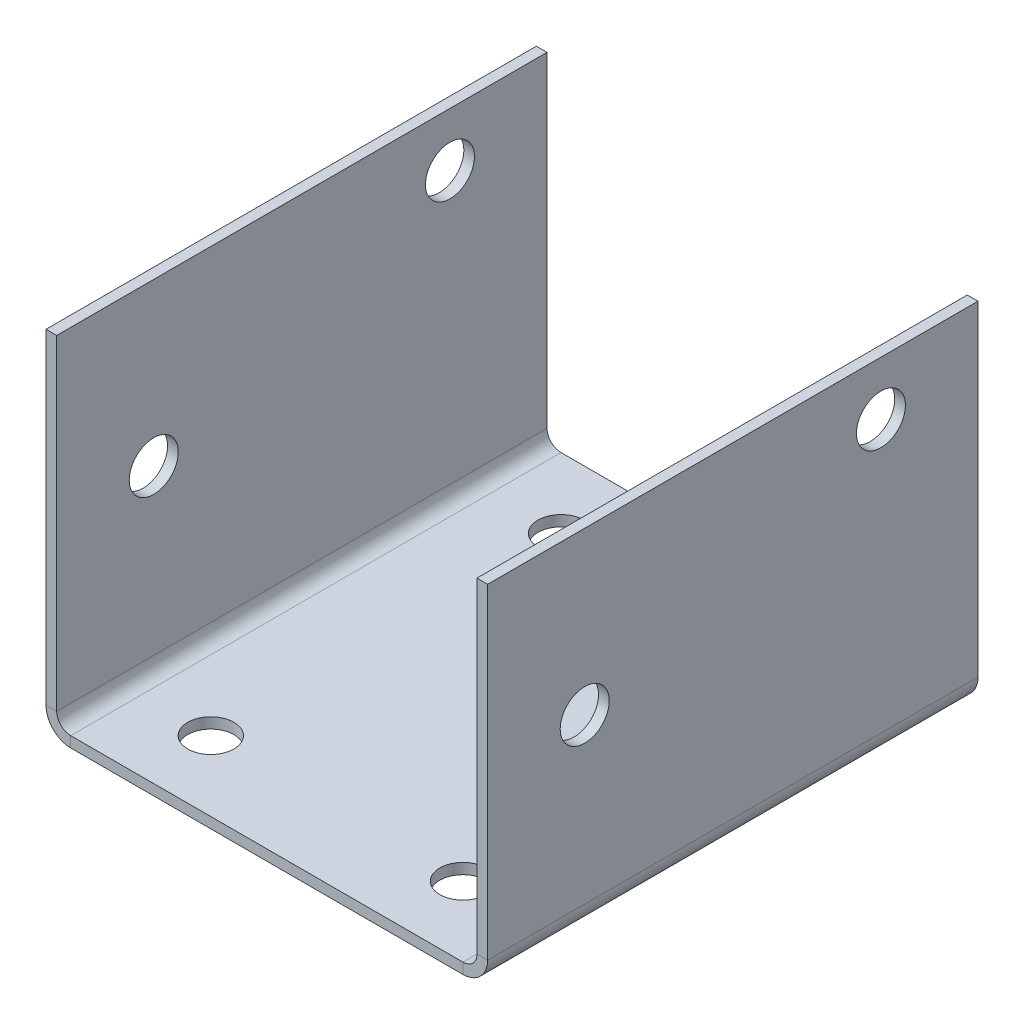
SolidWorks part; units mm, degrees
note: The reader was unsure of these and kept them because the rebuilt part matched: flange length of "Edge-Flange1".
ref_plane "Front Plane" through (0, 0, 0) normal (0, 0, 1) x (1, 0, 0)
ref_plane "Top Plane" through (0, 0, 0) normal (0, 1, 0) x (1, 0, 0)
ref_plane "Right Plane" through (0, 0, 0) normal (1, 0, 0) x (0, 0, -1)
sketch "Sketch1" plane through (0, 0, 0) normal (0, 1, 0) x (1, 0, 0)
  line L1 (-30, -35) -> (30, -35)
  line L2 (-30, -35) -> (-30, 35)
  line L3 (-30, 35) -> (30, 35)
  line L4 (30, -35) -> (30, 35)
  line L5 (-30, -35) -> (30, 35) construction
  line L6 (-30, 35) -> (30, -35) construction
  point P0 (0, 0)
  dimension "D1" = 60
  dimension "D2" = 70
base flange "Base-Flange3" sketch "Sketch1" thickness 1.524 reverse thickness direction no parameters "D1"=2
edge flange "Edge-Flange1" sketch "Sketch14" flange profiles "Sketch14", "Sketch15" flange angle 90 flange length 50 flange position material outside bend radius 2 thickness 1.524 relief rectangular parameters "D6"=10, "D8"=1
sketch "Sketch14" plane through (-30, 0, 0) normal (-1, 0, 0) x (0, 0, 1)
  line L0 (-35, 0) -> (35, 0) construction
  line L1 (-35, 0) -> (35, 0)
  line L2 (-35, 0) -> (-35, 48.476)
  line L3 (-35, 48.476) -> (35, 48.476)
  line L4 (35, 48.476) -> (35, 0)
sketch "Sketch15" plane through (30, 0, 0) normal (1, 0, 0) x (0, 0, -1)
  line L0 (-35, 0) -> (35, 0) construction
  line L1 (-35, 0) -> (35, 0)
  line L2 (-35, 0) -> (-35, 48.476)
  line L3 (-35, 48.476) -> (35, 48.476)
  line L4 (35, 48.476) -> (35, 0)
bend "EdgeBend1" bend radius 2 bend angle 90 parameters "D5"=1
bend "EdgeBend2" bend radius 2 bend angle 90 parameters "D5"=2
hole_wizard "Ø7.0 (7) Diameter Hole1" positions "Sketch20" profile "Sketch18" hole size "Ø7.0" standard "ANSI Metric" end condition through all
sketch "Sketch20" plane through (-31.524, 0, 0) normal (-1, 0, 0) x (0, 0, 1)
  line L0 (35, 0) -> (-35, 0) construction
  line L1 (-21.1431, 40.7909) -> (21.1431, 25.4) construction
  line L3 (21.1431, 25.4) -> (10.454, 25.4) construction
  point P0 (21.1431, 25.4)
  point P2 (-21.1431, 40.7909)
  point P15 (0, 33.0955)
  dimension "D1" = 25.4
  dimension "D2" = 45
  dimension "D3" = 20
sketch "Sketch18" plane through (-31.524, 25.4, 21.1431) normal (0, 1, 0) x (0, 0, 1)
  line L0 (0, 0) -> (0, 63.048)
  line L1 (0, 63.048) -> (3.5, 63.048)
  line L2 (3.5, 63.048) -> (3.5, 0)
  line L5 (3.5, 0) -> (0, 0)
  line L11 (0, -6.35) -> (0, 107.95) construction
  dimension "Thru Hole Dia." = 7
  dimension "Thru Hole Depth" = 63.048
hole_wizard "M6 Clearance Hole1" positions "Sketch23" profile "Sketch22" hole size "M6" standard "ANSI Metric" end condition through all
sketch "Sketch23" plane through (0, 0, 0) normal (0, 1, 0) x (1, 0, 0)
  line L0 (-28, -35) -> (28, -35) construction
  line L1 (-28, -35) -> (-28, 35) construction
  line L2 (28, 35) -> (28, -35) construction
  line L3 (28, 35) -> (-28, 35) construction
  point P0 (-18, -25)
  point P2 (18, -25)
  point P4 (18, 25)
  point P6 (-18, 25)
  point P11 (0, 0)
  point P18 (0, 0)
  point P19 (0, 0)
  dimension "D1" = 10
  dimension "D2" = 10
  dimension "D3" = 10
  dimension "D4" = 10
  dimension "D5" = 10
sketch "Sketch22" plane through (-18, 0, 25) normal (1, 0, 0) x (0, 0, 1)
  line L0 (0, 0) -> (0, 1.524)
  line L1 (0, 1.524) -> (3.3, 1.524)
  line L2 (3.3, 1.524) -> (3.3, 0)
  line L5 (3.3, 0) -> (0, 0)
  line L11 (0, -6.35) -> (0, 107.95) construction
  dimension "Thru Hole Dia." = 6.6
  dimension "Thru Hole Depth" = 1.524
sketch "Bend-Lines1" [suppressed] plane through (0, 0, 0) normal (0, 1, 0) x (1, 0, 0)
sketch "Bounding-Box1" [suppressed] plane through (0, 0, 0) normal (0, 1, 0) x (1, 0, 0)
sheet metal parameters "Sheet-Metal3" thickness 1.524 parameters "D1"=2
flat pattern "Flat-Pattern3" [suppressed]
sketch "Bend-Lines4" plane through (0, 0, 0) normal (0, 1, 0) x (1, 0, 0)
sketch3d "Bounding-Box4" [suppressed]
  line L0 (30, -35, 0) -> (30, 35, 0) construction
  line L1 (-30, -35, 0) -> (-30, 35, 0) construction
  line L2 (30, -35, 0) -> (-30, -35, 0) construction
  line L3 (30, 35, 0) -> (-30, 35, 0) construction
sheet metal parameters "Sheet-Metal4" thickness 1.524 parameters "D1"=2
flat pattern "Flat-Pattern3"
sketch "Bend-Lines4" plane through (0, 0, 0) normal (0, 1, 0) x (1, 0, 0)
  line L0 (30.1693, -35) -> (30.1693, 35) construction
  line L1 (-30.1693, 35) -> (-30.1693, -35) construction
  line L2 (30.1693, -35) -> (30.1693, 35) construction
  line L3 (-30.1693, 35) -> (-30.1693, -35) construction
sketch3d "Bounding-Box4" [suppressed]
  line L0 (78.8145, 35, 0) -> (-78.8145, 35, 0) construction
  line L1 (78.8145, -35, 0) -> (-78.8145, -35, 0) construction
  line L2 (78.8145, 35, 0) -> (78.8145, -35, 0) construction
  line L3 (-78.8145, 35, 0) -> (-78.8145, -35, 0) construction
bend of the flat pattern "Flatten-<EdgeBend1>1"
bend of the flat pattern "Flatten-<EdgeBend2>1"
sheet metal parameters "Sheet-Metal5" thickness 1.524 parameters "D1"=2
flat pattern "Flat-Pattern3"
sketch "Bend-Lines4" plane through (0, 0, 0) normal (0, 1, 0) x (1, 0, 0)
  line L0 (30.1693, -35) -> (30.1693, 35) construction
  line L1 (-30.1693, 35) -> (-30.1693, -35) construction
  line L2 (30.1693, -35) -> (30.1693, 35) construction
  line L3 (-30.1693, 35) -> (-30.1693, -35) construction
sketch3d "Bounding-Box4" [suppressed]
  line L0 (78.8145, 35, 0) -> (-78.8145, 35, 0) construction
  line L1 (78.8145, -35, 0) -> (-78.8145, -35, 0) construction
  line L2 (78.8145, 35, 0) -> (78.8145, -35, 0) construction
  line L3 (-78.8145, 35, 0) -> (-78.8145, -35, 0) construction
bend of the flat pattern "Flatten-<EdgeBend1>1"
bend of the flat pattern "Flatten-<EdgeBend2>1"
sheet metal parameters "Sheet-Metal6" thickness 1.524 parameters "D1"=2
flat pattern "Flat-Pattern3"
sketch "Bend-Lines4" plane through (0, 0, 0) normal (0, 1, 0) x (1, 0, 0)
  line L0 (30.1693, -35) -> (30.1693, 35) construction
  line L1 (-30.1693, 35) -> (-30.1693, -35) construction
  line L2 (30.1693, -35) -> (30.1693, 35) construction
  line L3 (-30.1693, 35) -> (-30.1693, -35) construction
sketch3d "Bounding-Box4" [suppressed]
  line L0 (78.8145, 35, 0) -> (-78.8145, 35, 0) construction
  line L1 (78.8145, -35, 0) -> (-78.8145, -35, 0) construction
  line L2 (78.8145, 35, 0) -> (78.8145, -35, 0) construction
  line L3 (-78.8145, 35, 0) -> (-78.8145, -35, 0) construction
bend of the flat pattern "Flatten-<EdgeBend1>1"
bend of the flat pattern "Flatten-<EdgeBend2>1"
